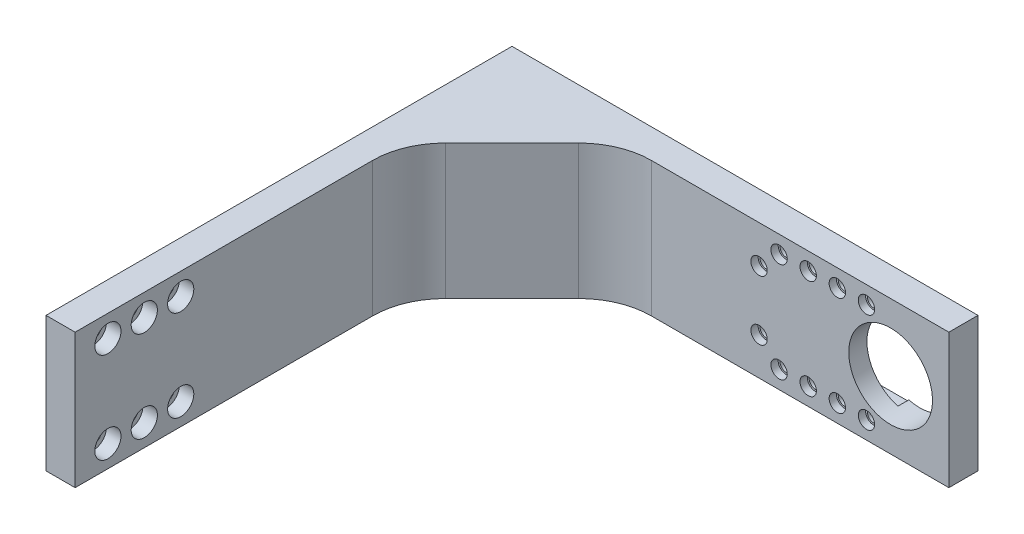
SolidWorks part; units mm, degrees
ref_plane "Front Plane" through (0, 0, 0) normal (0, 0, 1) x (1, 0, 0)
ref_plane "Top Plane" through (0, 0, 0) normal (0, 1, 0) x (1, 0, 0)
ref_plane "Right Plane" through (0, 0, 0) normal (1, 0, 0) x (0, 0, -1)
sketch "Sketch1" plane through (0, 0, 0) normal (0, 1, 0) x (1, 0, 0)
  line L0 (0, 0) -> (0, 128)
  line L1 (0, 128) -> (128, 128)
  line L2 (128, 128) -> (128, 120)
  line L3 (128, 120) -> (8, 120)
  line L4 (8, 120) -> (8, 0)
  line L5 (8, 0) -> (0, 0)
  dimension "D1" = 120
  dimension "D2" = 120
  dimension "D3" = 128
  dimension "D4" = 128
extrude "Boss-Extrude1" add sketch "Sketch1" along normal blind 37
sketch "Sketch2" plane through (0, 0, -128) normal (0, 0, -1) x (-1, 0, 0)
  line L0 (-128, 18.5) -> (-112, 18.5)
  line L1 (-128, 37) -> (-128, 0) construction
  circle A0 centre (-112, 18.5) radius 11.5
  dimension "D2" = 23
  dimension "D1" = 16
extrude "Cut-Extrude1" cut sketch "Sketch2" against normal up to next contours A0 region at (112, 7.3253, -128)
sketch "Sketch3" plane through (0, 0, -128) normal (0, 0, -1) x (-1, 0, 0)
  line L0 (-128, 18.5) -> (-71.8119, 18.5)
  line L2 (-128, 37) -> (-128, 0) construction
  circle A0 centre (-105.36, 32.19) radius 1.75
  circle A1 centre (-97.36, 32.19) radius 1.75
  circle A2 centre (-89.36, 32.19) radius 1.75
  circle A3 centre (-81.36, 32.19) radius 1.75
  circle A4 centre (-81.36, 4.81) radius 1.75
  circle A5 centre (-89.36, 4.81) radius 1.75
  circle A6 centre (-97.36, 4.81) radius 1.75
  circle A7 centre (-105.36, 4.81) radius 1.75
  circle A8 centre (-75.86, 26.69) radius 1.75
  circle A9 centre (-75.86, 10.31) radius 1.75
  dimension "D3" = 3.5
  dimension "D6" = 3.5
  dimension "D7" = 3.5
  dimension "D1" = 4
extrude "Cut-Extrude2" cut sketch "Sketch3" against normal up to next contours A9 | A0 | A1 | A2 | A3 | A4 | A5 | A6 | A7 | A8 region at (75.86, 10.31, -128)
sketch "Sketch5" plane through (0, 0, -128) normal (0, 0, -1) x (-1, 0, 0)
  line L0 (-109, 7) -> (-109, 30)
  line L4 (-109, 30) -> (-71, 30)
  line L5 (-71, 30) -> (-71, 7)
  line L6 (-71, 7) -> (-109, 7)
  dimension "D3" = 23
  dimension "D4" = 38
  dimension "D5" = 38
extrude "Cut-Extrude3" cut sketch "Sketch5" against normal blind 3
sketch "Sketch6" plane through (71, 0, 0) normal (1, 0, 0) x (0, 0, -1)
  line L4 (128, 7) -> (128, 30)
  line L5 (128, 30) -> (125, 30)
  line L6 (125, 30) -> (125, 7)
  line L7 (125, 7) -> (128, 7)
  line L8 (128, 7) -> (128, 30)
  line L9 (128, 30) -> (125, 30)
  line L10 (125, 30) -> (125, 7)
  line L11 (125, 7) -> (128, 7)
  dimension "D1" = 0
extrude "Boss-Extrude2" add sketch "Sketch6" along normal blind 7.5
sketch "Sketch7" plane through (0, 0, -125) normal (0, 0, 1) x (1, 0, 0)
  circle A0 centre (75.86, 10.31) radius 1.75 construction
  circle A1 centre (75.86, 26.69) radius 1.75 construction
  circle A2 centre (75.86, 10.31) radius 1.75
  circle A3 centre (75.86, 26.69) radius 1.75
extrude "Cut-Extrude4" cut sketch "Sketch7" against normal up to next
sketch "Sketch8" plane through (0, 0, -120) normal (0, 0, 1) x (1, 0, 0)
  circle A0 centre (75.86, 10.31) radius 2.25
  circle A1 centre (75.86, 26.69) radius 2.25
  circle A2 centre (81.36, 32.19) radius 2.25
  circle A3 centre (89.36, 32.19) radius 2.25
  circle A4 centre (97.36, 32.19) radius 2.25
  circle A5 centre (105.36, 32.19) radius 2.25
  circle A6 centre (105.36, 4.81) radius 2.25
  circle A7 centre (97.36, 4.81) radius 2.25
  circle A8 centre (89.36, 4.81) radius 2.25
  circle A9 centre (81.36, 4.81) radius 2.25
  dimension "D1" = 4.5
  dimension "D2" = 4.5
  dimension "D3" = 4.5
  dimension "D4" = 4.5
  dimension "D5" = 4.5
  dimension "D6" = 4.5
  dimension "D7" = 4.5
  dimension "D8" = 4.5
  dimension "D9" = 4.5
  dimension "D10" = 4.5
extrude "Cut-Extrude5" cut sketch "Sketch8" against normal blind 2
sketch "Sketch9" plane through (8, 0, 0) normal (1, 0, 0) x (0, 0, -1)
  circle A0 centre (9, 6) radius 2.25
  circle A1 centre (19, 6) radius 2.25
  circle A2 centre (29, 6) radius 2.25
  circle A3 centre (29, 31) radius 2.25
  circle A4 centre (9, 31) radius 2.25
  circle A5 centre (19, 31) radius 2.25
  dimension "D3" = 4.5
  dimension "D4" = 3
extrude "Cut-Extrude6" cut sketch "Sketch9" against normal up to next contours A3 | A5 | A4 | A1 | A2 | A0 region at (8, 6, -19) region at (8, 6, -29) region at (8, 31, -29) region at (8, 31, -9) region at (8, 31, -19)
sketch "Sketch10" plane through (8, 0, 0) normal (1, 0, 0) x (0, 0, -1)
  circle A0 centre (9, 31) radius 3.6
  circle A1 centre (19, 31) radius 3.6
  circle A2 centre (29, 31) radius 3.6
  circle A3 centre (29, 6) radius 3.6
  circle A4 centre (19, 6) radius 3.6
  circle A5 centre (9, 6) radius 3.6
  dimension "D1" = 7.2
  dimension "D2" = 7.2
  dimension "D3" = 7.2
  dimension "D4" = 7.2
  dimension "D5" = 7.2
  dimension "D6" = 7.2
extrude "Cut-Extrude7" cut sketch "Sketch10" against normal blind 4
chamfer "Chamfer1" distance 30 angle 45 1 edges at (8, 18.5, -120)
fillet "Fillet4" radius 20 2 edges at (38, 18.5, -120) (8, 18.5, -90)
